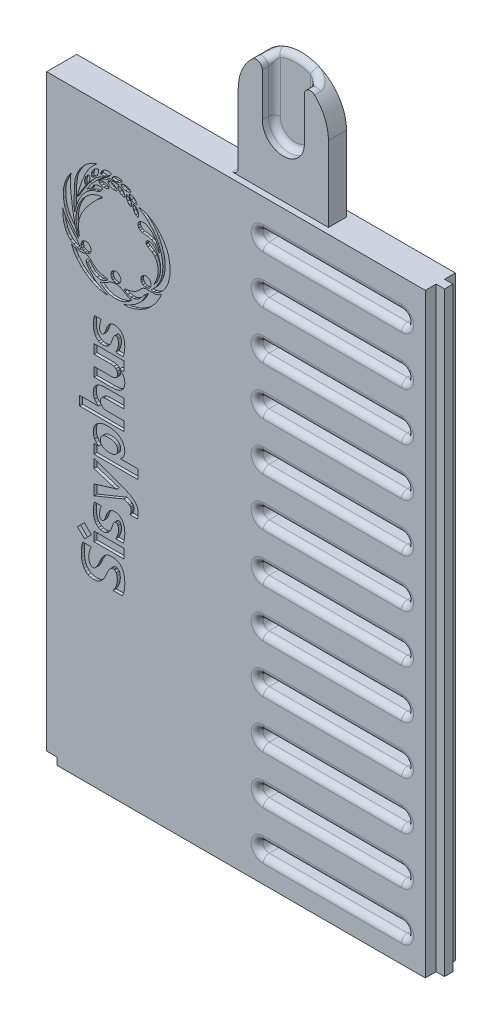
SolidWorks part; units mm, degrees
material "PVC Rigid"
ref_plane "Front Plane" through (0, 0, 0) normal (0, 0, 1) x (1, 0, 0)
ref_plane "Top Plane" through (0, 0, 0) normal (0, 1, 0) x (1, 0, 0)
ref_plane "Right Plane" through (0, 0, 0) normal (1, 0, 0) x (0, 0, -1)
sketch "Sketch1" plane through (0, 0, 0) normal (0, 1, 0) x (1, 0, 0)
  line L1 (-38.35, 2.5) -> (38.35, 2.5)
  line L2 (-38.35, 2.5) -> (-38.35, -2.5)
  line L3 (-38.35, -2.5) -> (38.35, -2.5)
  line L4 (38.35, 2.5) -> (38.35, -2.5)
  line L5 (-38.35, 2.5) -> (38.35, -2.5) construction
  line L6 (-38.35, -2.5) -> (38.35, 2.5) construction
  point P0 (0, 0)
  dimension "D1" = 5
  dimension "D2" = 76.7
extrude "Boss-Extrude1" add sketch "Sketch1" along normal blind 99
sketch "Sketch2" plane through (0, 99, 0) normal (0, 1, 0) x (1, 0, 0)
  line L0 (-7.5, -1.5) -> (-7.5, -0.5)
  line L1 (-6.5, 1.5) -> (7.5, 1.5)
  line L2 (-7.5, 0.5) -> (-7.5, -0.5)
  line L3 (-6.5, -1.5) -> (7.5, -1.5)
  line L5 (-7.5, 1.5) -> (7.5, -1.5) construction
  line L6 (-7.5, -1.5) -> (7.5, 1.5) construction
  line L7 (-7.5, 1.5) -> (-6.5, 1.5)
  line L8 (-7.5, -1.5) -> (-6.5, -1.5)
  line L9 (7.5, 1.5) -> (7.5, -1.5)
  line L12 (-7.5, 0.5) -> (-7.5, 1.5)
  point P0 (0, 0)
  dimension "D1" = 15
  dimension "D2" = 3
extrude "Boss-Extrude2" add sketch "Sketch2" along normal blind 20
sketch "Sketch3" plane through (0, 0, 1.5) normal (0, 0, 1) x (1, 0, 0)
  line L0 (-7.5, 119) -> (7.5, 119) construction
  line L1 (-3.5, 119) -> (3.5, 119)
  line L2 (-3.5, 119) -> (-3.5, 109)
  line L4 (3.5, 119) -> (3.5, 109)
  line L5 (-7.5, 119) -> (-7.5, 99) construction
  arc A0 (-3.5, 109) -> (3.5, 109) centre (0, 109) ccw
  dimension "D3" = 7.5
  dimension "D1" = 7
  dimension "D2" = 10
fillet "Fillet2" radius 1 1 edges at (-7.5, 99, 0)
sketch "Sketch4" plane through (0, 99, 0) normal (0, 1, 0) x (1, 0, 0)
  line L4 (-36.15, 0.5653) -> (-38.65, 0.5653)
  line L5 (-36.15, -1.4347) -> (-36.15, 0.5653)
  line L6 (-38.65, -1.4347) -> (-36.15, -1.4347)
  line L7 (-38.65, 0.5653) -> (-38.65, -1.4347)
  line L8 (-36.15, 0.5653) -> (-38.65, 0.5653)
  line L9 (-36.15, -1.4347) -> (-36.15, 0.5653)
  line L10 (-38.65, -1.4347) -> (-36.15, -1.4347)
  line L11 (-38.65, 0.5653) -> (-38.65, -1.4347)
  dimension "D1" = 0
sketch "Sketch5" plane through (0, 0, 0) normal (0, 0, 1) x (1, 0, 0)
  line L1 (24.6, -5) -> (60, -5)
  line L2 (24.6, -5) -> (24.6, 130)
  line L3 (24.6, 130) -> (60, 130)
  line L4 (60, -5) -> (60, 130)
extrude "Trim_door_beside_fixed_buttons" cut sketch "Sketch5" along normal blind 20 from offset 10 offset against normal yes
sketch "Sketch6" plane through (0, 0, 0) normal (0, 0, 1) x (1, 0, 0)
  line L0 (-39, -1) -> (-36.6, -1)
  line L1 (-36.6, -1) -> (-36.6, 1.2)
  line L2 (-36.6, 1.2) -> (-39, 1.2)
  line L3 (-39, 1.2) -> (-39, -1)
extrude "Clear_original_end_corner" cut sketch "Sketch6" along normal blind 10 from offset 5 offset against normal yes
sketch "Sketch8" plane through (0, 0, 0) normal (0, 0, 1) x (1, 0, 0)
  line L0 (24, 0) -> (26, 0)
  line L1 (26, 0) -> (26, 99)
  line L2 (26, 99) -> (24, 99)
  line L3 (24, 99) -> (24, 0)
extrude "Dust_overlap_tongue" add sketch "Sketch8" along normal blind 1.4 from offset 0.7 offset against normal yes
sketch "Sketch13" plane through (0, 0, 0) normal (0, 0, 1) x (1, 0, 0)
  line L0 (-25.7438, 29.8438) -> (-27.3063, 29.8438)
  line L1 (-27.3063, 29.8438) -> (-26.9938, 30.2875)
  line L2 (-26.9938, 30.2875) -> (-26.7688, 30.7688)
  line L3 (-26.7688, 30.7688) -> (-26.6375, 31.2688)
  line L4 (-26.6375, 31.2688) -> (-26.5938, 31.775)
  line L5 (-26.5938, 31.775) -> (-26.6438, 32.2938)
  line L6 (-26.6438, 32.2938) -> (-26.7063, 32.5)
  line L7 (-26.7063, 32.5) -> (-26.7938, 32.6625)
  line L8 (-26.7938, 32.6625) -> (-27.0188, 32.8875)
  line L9 (-27.0188, 32.8875) -> (-27.1563, 32.9438)
  line L10 (-27.1563, 32.9438) -> (-27.3, 32.9563)
  line L11 (-27.3, 32.9563) -> (-27.4938, 32.9313)
  line L12 (-27.4938, 32.9313) -> (-27.6688, 32.8438)
  line L13 (-27.6688, 32.8438) -> (-27.9625, 32.525)
  line L14 (-27.9625, 32.525) -> (-28.2313, 32.0438)
  line L15 (-28.2313, 32.0438) -> (-28.4875, 31.4375)
  line L16 (-28.4875, 31.4375) -> (-28.6688, 31.0563)
  line L17 (-28.6688, 31.0563) -> (-28.8687, 30.725)
  line L18 (-28.8687, 30.725) -> (-29.0875, 30.4438)
  line L19 (-29.0875, 30.4438) -> (-29.325, 30.2188)
  line L20 (-29.325, 30.2188) -> (-29.5813, 30.0438)
  line L21 (-29.5813, 30.0438) -> (-29.8687, 29.9125)
  line L22 (-29.8687, 29.9125) -> (-30.175, 29.8375)
  line L23 (-30.175, 29.8375) -> (-30.5125, 29.8125)
  line L24 (-30.5125, 29.8125) -> (-31.025, 29.8688)
  line L25 (-31.025, 29.8688) -> (-31.4563, 30.0313)
  line L26 (-31.4563, 30.0313) -> (-31.8125, 30.2938)
  line L27 (-31.8125, 30.2938) -> (-32.1, 30.6313)
  line L28 (-32.1, 30.6313) -> (-32.3188, 31.0438)
  line L29 (-32.3188, 31.0438) -> (-32.475, 31.5063)
  line L30 (-32.475, 31.5063) -> (-32.5625, 32.025)
  line L31 (-32.5625, 32.025) -> (-32.5938, 32.5625)
  line L32 (-32.5938, 32.5625) -> (-32.575, 33.0813)
  line L33 (-32.575, 33.0813) -> (-32.525, 33.5313)
  line L34 (-32.525, 33.5313) -> (-32.4438, 33.9375)
  line L35 (-32.4438, 33.9375) -> (-32.325, 34.3125)
  line L36 (-32.325, 34.3125) -> (-30.8625, 34.3125)
  line L37 (-30.8625, 34.3125) -> (-31.0813, 33.9313)
  line L38 (-31.0813, 33.9313) -> (-31.2313, 33.5)
  line L39 (-31.2313, 33.5) -> (-31.325, 33.0625)
  line L40 (-31.325, 33.0625) -> (-31.3563, 32.65)
  line L41 (-31.3563, 32.65) -> (-31.3, 32.1625)
  line L42 (-31.3, 32.1625) -> (-31.1563, 31.7938)
  line L43 (-31.1563, 31.7938) -> (-30.9375, 31.5563)
  line L44 (-30.9375, 31.5563) -> (-30.8, 31.4938)
  line L45 (-30.8, 31.4938) -> (-30.6438, 31.475)
  line L46 (-30.6438, 31.475) -> (-30.4813, 31.5)
  line L47 (-30.4813, 31.5) -> (-30.3313, 31.5688)
  line L48 (-30.3313, 31.5688) -> (-30.0688, 31.8313)
  line L49 (-30.0688, 31.8313) -> (-29.825, 32.2438)
  line L50 (-29.825, 32.2438) -> (-29.575, 32.8)
  line L51 (-29.575, 32.8) -> (-29.3938, 33.1938)
  line L52 (-29.3938, 33.1938) -> (-29.2, 33.55)
  line L53 (-29.2, 33.55) -> (-28.9937, 33.8625)
  line L54 (-28.9937, 33.8625) -> (-28.7563, 34.125)
  line L55 (-28.7563, 34.125) -> (-28.4875, 34.3375)
  line L56 (-28.4875, 34.3375) -> (-28.1875, 34.4938)
  line L57 (-28.1875, 34.4938) -> (-27.8438, 34.5875)
  line L58 (-27.8438, 34.5875) -> (-27.4438, 34.6188)
  line L59 (-27.4438, 34.6188) -> (-26.9, 34.5625)
  line L60 (-26.9, 34.5625) -> (-26.4563, 34.4)
  line L61 (-26.4563, 34.4) -> (-26.1, 34.1375)
  line L62 (-26.1, 34.1375) -> (-25.8125, 33.7938)
  line L63 (-25.8125, 33.7938) -> (-25.6, 33.3813)
  line L64 (-25.6, 33.3813) -> (-25.4625, 32.9063)
  line L65 (-25.4625, 32.9063) -> (-25.375, 32.3875)
  line L66 (-25.375, 32.3875) -> (-25.35, 31.8438)
  line L67 (-25.35, 31.8438) -> (-25.375, 31.2813)
  line L68 (-25.375, 31.2813) -> (-25.45, 30.7438)
  line L69 (-25.45, 30.7438) -> (-25.5688, 30.2625)
  line L70 (-25.5688, 30.2625) -> (-25.7438, 29.8438)
  line L71 (-32.0594, 34.9016) -> (-33.2172, 36.0594)
  line L72 (-33.2172, 36.0594) -> (-32.0594, 37.2172)
  line L73 (-32.0594, 37.2172) -> (-30.9016, 36.0594)
  line L74 (-30.9016, 36.0594) -> (-32.0594, 34.9016)
  line L75 (-25.475, 36.8188) -> (-25.475, 35.275)
  line L76 (-25.475, 35.275) -> (-30.475, 35.275)
  line L77 (-30.475, 35.275) -> (-30.475, 36.8188)
  line L78 (-30.475, 36.8188) -> (-25.475, 36.8188)
  line L79 (-25.6063, 37.5) -> (-26.8563, 37.5)
  line L80 (-26.8563, 37.5) -> (-26.6563, 37.8813)
  line L81 (-26.6563, 37.8813) -> (-26.5125, 38.2625)
  line L82 (-26.5125, 38.2625) -> (-26.425, 38.6313)
  line L83 (-26.425, 38.6313) -> (-26.4, 38.975)
  line L84 (-26.4, 38.975) -> (-26.425, 39.3438)
  line L85 (-26.425, 39.3438) -> (-26.5125, 39.6188)
  line L86 (-26.5125, 39.6188) -> (-26.6563, 39.8)
  line L87 (-26.6563, 39.8) -> (-26.8563, 39.8563)
  line L88 (-26.8563, 39.8563) -> (-26.9938, 39.8313)
  line L89 (-26.9938, 39.8313) -> (-27.1, 39.75)
  line L90 (-27.1, 39.75) -> (-27.2688, 39.475)
  line L91 (-27.2688, 39.475) -> (-27.4063, 39.1063)
  line L92 (-27.4063, 39.1063) -> (-27.5375, 38.7188)
  line L93 (-27.5375, 38.7188) -> (-27.775, 38.1938)
  line L94 (-27.775, 38.1938) -> (-28.075, 37.8125)
  line L95 (-28.075, 37.8125) -> (-28.475, 37.5813)
  line L96 (-28.475, 37.5813) -> (-28.7188, 37.5188)
  line L97 (-28.7188, 37.5188) -> (-29.0063, 37.5)
  line L98 (-29.0063, 37.5) -> (-29.3938, 37.5438)
  line L99 (-29.3938, 37.5438) -> (-29.725, 37.6813)
  line L100 (-29.725, 37.6813) -> (-30, 37.9)
  line L101 (-30, 37.9) -> (-30.225, 38.1688)
  line L102 (-30.225, 38.1688) -> (-30.3875, 38.5)
  line L103 (-30.3875, 38.5) -> (-30.5063, 38.8688)
  line L104 (-30.5063, 38.8688) -> (-30.575, 39.2688)
  line L105 (-30.575, 39.2688) -> (-30.6, 39.6875)
  line L106 (-30.6, 39.6875) -> (-30.5438, 40.3625)
  line L107 (-30.5438, 40.3625) -> (-30.3938, 41.0375)
  line L108 (-30.3938, 41.0375) -> (-29.2063, 41.0375)
  line L109 (-29.2063, 41.0375) -> (-29.3563, 40.7313)
  line L110 (-29.3563, 40.7313) -> (-29.4625, 40.4063)
  line L111 (-29.4625, 40.4063) -> (-29.525, 40.0813)
  line L112 (-29.525, 40.0813) -> (-29.55, 39.75)
  line L113 (-29.55, 39.75) -> (-29.5188, 39.4625)
  line L114 (-29.5188, 39.4625) -> (-29.4438, 39.2313)
  line L115 (-29.4438, 39.2313) -> (-29.3125, 39.0688)
  line L116 (-29.3125, 39.0688) -> (-29.125, 39.0063)
  line L117 (-29.125, 39.0063) -> (-29, 39.0313)
  line L118 (-29, 39.0313) -> (-28.8938, 39.0938)
  line L119 (-28.8938, 39.0938) -> (-28.725, 39.325)
  line L120 (-28.725, 39.325) -> (-28.6, 39.6438)
  line L121 (-28.6, 39.6438) -> (-28.4813, 39.9875)
  line L122 (-28.4813, 39.9875) -> (-28.25, 40.5438)
  line L123 (-28.25, 40.5438) -> (-27.95, 40.9688)
  line L124 (-27.95, 40.9688) -> (-27.7625, 41.125)
  line L125 (-27.7625, 41.125) -> (-27.55, 41.2438)
  line L126 (-27.55, 41.2438) -> (-27.3, 41.3125)
  line L127 (-27.3, 41.3125) -> (-27.0063, 41.3375)
  line L128 (-27.0063, 41.3375) -> (-26.5938, 41.2875)
  line L129 (-26.5938, 41.2875) -> (-26.2438, 41.1438)
  line L130 (-26.2438, 41.1438) -> (-25.9563, 40.9188)
  line L131 (-25.9563, 40.9188) -> (-25.7313, 40.6313)
  line L132 (-25.7313, 40.6313) -> (-25.5625, 40.2875)
  line L133 (-25.5625, 40.2875) -> (-25.4438, 39.8938)
  line L134 (-25.4438, 39.8938) -> (-25.375, 39.4688)
  line L135 (-25.375, 39.4688) -> (-25.35, 39.0313)
  line L136 (-25.35, 39.0313) -> (-25.4125, 38.2375)
  line L137 (-25.4125, 38.2375) -> (-25.6063, 37.5)
  line L138 (-30.475, 47.3188) -> (-25.075, 45.2875)
  line L139 (-25.075, 45.2875) -> (-24.6188, 45.0938)
  line L140 (-24.6188, 45.0938) -> (-24.2188, 44.875)
  line L141 (-24.2188, 44.875) -> (-23.8875, 44.6313)
  line L142 (-23.8875, 44.6313) -> (-23.6125, 44.3688)
  line L143 (-23.6125, 44.3688) -> (-23.4, 44.0813)
  line L144 (-23.4, 44.0813) -> (-23.2438, 43.7688)
  line L145 (-23.2438, 43.7688) -> (-23.1562, 43.4375)
  line L146 (-23.1562, 43.4375) -> (-23.125, 43.0813)
  line L147 (-23.125, 43.0813) -> (-23.1562, 42.5688)
  line L148 (-23.1562, 42.5688) -> (-23.2563, 42.1563)
  line L149 (-23.2563, 42.1563) -> (-24.4813, 42.1563)
  line L150 (-24.4813, 42.1563) -> (-24.3438, 42.4813)
  line L151 (-24.3438, 42.4813) -> (-24.3, 42.825)
  line L152 (-24.3, 42.825) -> (-24.3375, 43.1)
  line L153 (-24.3375, 43.1) -> (-24.4375, 43.3313)
  line L154 (-24.4375, 43.3313) -> (-24.6188, 43.5188)
  line L155 (-24.6188, 43.5188) -> (-24.8625, 43.6563)
  line L156 (-24.8625, 43.6563) -> (-25.4875, 43.9188)
  line L157 (-25.4875, 43.9188) -> (-30.475, 41.8875)
  line L158 (-30.475, 41.8875) -> (-30.475, 43.6)
  line L159 (-30.475, 43.6) -> (-27.4313, 44.5313)
  line L160 (-27.4313, 44.5313) -> (-27.125, 44.6125)
  line L161 (-27.125, 44.6125) -> (-26.7625, 44.6688)
  line L162 (-26.7625, 44.6688) -> (-26.7625, 44.6875)
  line L163 (-26.7625, 44.6875) -> (-27.0688, 44.75)
  line L164 (-27.0688, 44.75) -> (-27.425, 44.85)
  line L165 (-27.425, 44.85) -> (-30.475, 45.7938)
  line L166 (-30.475, 45.7938) -> (-30.475, 47.3188)
  line L167 (-26.0563, 49.4312) -> (-26.0563, 49.4125)
  line L168 (-26.0563, 49.4125) -> (-23.175, 49.4125)
  line L169 (-23.175, 49.4125) -> (-23.175, 47.8687)
  line L170 (-23.175, 47.8687) -> (-30.475, 47.8687)
  line L171 (-30.475, 47.8687) -> (-30.475, 49.4125)
  line L172 (-30.475, 49.4125) -> (-29.725, 49.4125)
  line L173 (-29.725, 49.4125) -> (-29.725, 49.4312)
  line L174 (-29.725, 49.4312) -> (-30.1063, 49.7437)
  line L175 (-30.1063, 49.7437) -> (-30.3813, 50.1187)
  line L176 (-30.3813, 50.1187) -> (-30.5438, 50.55)
  line L177 (-30.5438, 50.55) -> (-30.6, 51.0375)
  line L178 (-30.6, 51.0375) -> (-30.5563, 51.5)
  line L179 (-30.5563, 51.5) -> (-30.4313, 51.9)
  line L180 (-30.4313, 51.9) -> (-30.225, 52.25)
  line L181 (-30.225, 52.25) -> (-29.9313, 52.5437)
  line L182 (-29.9313, 52.5437) -> (-29.5688, 52.775)
  line L183 (-29.5688, 52.775) -> (-29.1438, 52.9375)
  line L184 (-29.1438, 52.9375) -> (-28.6625, 53.0375)
  line L185 (-28.6625, 53.0375) -> (-28.1188, 53.0687)
  line L186 (-28.1188, 53.0687) -> (-27.525, 53.0313)
  line L187 (-27.525, 53.0313) -> (-26.9875, 52.9125)
  line L188 (-26.9875, 52.9125) -> (-26.5188, 52.725)
  line L189 (-26.5188, 52.725) -> (-26.1125, 52.4562)
  line L190 (-26.1125, 52.4562) -> (-25.7813, 52.1187)
  line L191 (-25.7813, 52.1187) -> (-25.5438, 51.7375)
  line L192 (-25.5438, 51.7375) -> (-25.4, 51.3)
  line L193 (-25.4, 51.3) -> (-25.35, 50.8125)
  line L194 (-25.35, 50.8125) -> (-25.3938, 50.3875)
  line L195 (-25.3938, 50.3875) -> (-25.525, 50.0125)
  line L196 (-25.525, 50.0125) -> (-25.75, 49.6937)
  line L197 (-25.75, 49.6937) -> (-26.0563, 49.4312)
  line L198 (-28.1063, 49.3875) -> (-27.7063, 49.3875)
  line L199 (-27.7063, 49.3875) -> (-27.2375, 49.4562)
  line L200 (-27.2375, 49.4562) -> (-26.8625, 49.6625)
  line L201 (-26.8625, 49.6625) -> (-26.7188, 49.8125)
  line L202 (-26.7188, 49.8125) -> (-26.6188, 49.9812)
  line L203 (-26.6188, 49.9812) -> (-26.5563, 50.1687)
  line L204 (-26.5563, 50.1687) -> (-26.5375, 50.3812)
  line L205 (-26.5375, 50.3812) -> (-26.5625, 50.6312)
  line L206 (-26.5625, 50.6312) -> (-26.6375, 50.85)
  line L207 (-26.6375, 50.85) -> (-26.7625, 51.0375)
  line L208 (-26.7625, 51.0375) -> (-26.9438, 51.2)
  line L209 (-26.9438, 51.2) -> (-27.1688, 51.325)
  line L210 (-27.1688, 51.325) -> (-27.4375, 51.4187)
  line L211 (-27.4375, 51.4187) -> (-27.7438, 51.4688)
  line L212 (-27.7438, 51.4688) -> (-28.1, 51.4875)
  line L213 (-28.1, 51.4875) -> (-28.4063, 51.4688)
  line L214 (-28.4063, 51.4688) -> (-28.675, 51.425)
  line L215 (-28.675, 51.425) -> (-28.9, 51.3438)
  line L216 (-28.9, 51.3438) -> (-29.0813, 51.2312)
  line L217 (-29.0813, 51.2312) -> (-29.225, 51.0875)
  line L218 (-29.225, 51.0875) -> (-29.3313, 50.9125)
  line L219 (-29.3313, 50.9125) -> (-29.3938, 50.7062)
  line L220 (-29.3938, 50.7062) -> (-29.4125, 50.4625)
  line L221 (-29.4125, 50.4625) -> (-29.3875, 50.2375)
  line L222 (-29.3875, 50.2375) -> (-29.325, 50.0313)
  line L223 (-29.325, 50.0313) -> (-29.2125, 49.85)
  line L224 (-29.2125, 49.85) -> (-29.0562, 49.6875)
  line L225 (-29.0562, 49.6875) -> (-28.6375, 49.4625)
  line L226 (-28.6375, 49.4625) -> (-28.1063, 49.3875)
  line L227 (-25.475, 58.4187) -> (-25.475, 56.8812)
  line L228 (-25.475, 56.8812) -> (-28.3188, 56.8812)
  line L229 (-28.3188, 56.8812) -> (-28.8, 56.8312)
  line L230 (-28.8, 56.8312) -> (-29.1375, 56.6812)
  line L231 (-29.1375, 56.6812) -> (-29.3438, 56.4312)
  line L232 (-29.3438, 56.4312) -> (-29.4125, 56.0812)
  line L233 (-29.4125, 56.0812) -> (-29.3938, 55.8875)
  line L234 (-29.3938, 55.8875) -> (-29.3375, 55.7125)
  line L235 (-29.3375, 55.7125) -> (-29.2437, 55.5562)
  line L236 (-29.2437, 55.5562) -> (-29.1063, 55.4187)
  line L237 (-29.1063, 55.4187) -> (-28.7563, 55.225)
  line L238 (-28.7563, 55.225) -> (-28.325, 55.1625)
  line L239 (-28.325, 55.1625) -> (-25.475, 55.1625)
  line L240 (-25.475, 55.1625) -> (-25.475, 53.6187)
  line L241 (-25.475, 53.6187) -> (-32.875, 53.6187)
  line L242 (-32.875, 53.6187) -> (-32.875, 55.1625)
  line L243 (-32.875, 55.1625) -> (-29.7313, 55.1625)
  line L244 (-29.7313, 55.1625) -> (-29.7313, 55.1812)
  line L245 (-29.7313, 55.1812) -> (-30.1125, 55.4937)
  line L246 (-30.1125, 55.4937) -> (-30.3813, 55.85)
  line L247 (-30.3813, 55.85) -> (-30.5438, 56.2625)
  line L248 (-30.5438, 56.2625) -> (-30.6, 56.7187)
  line L249 (-30.6, 56.7187) -> (-30.5688, 57.1187)
  line L250 (-30.5688, 57.1187) -> (-30.4688, 57.4625)
  line L251 (-30.4688, 57.4625) -> (-30.3125, 57.7562)
  line L252 (-30.3125, 57.7562) -> (-30.0875, 57.9937)
  line L253 (-30.0875, 57.9937) -> (-29.7938, 58.1812)
  line L254 (-29.7938, 58.1812) -> (-29.4438, 58.3125)
  line L255 (-29.4438, 58.3125) -> (-29.025, 58.3937)
  line L256 (-29.025, 58.3937) -> (-28.5438, 58.4187)
  line L257 (-28.5438, 58.4187) -> (-25.475, 58.4187)
  line L258 (-25.475, 63.8) -> (-25.475, 62.2562)
  line L259 (-25.475, 62.2562) -> (-26.2375, 62.2562)
  line L260 (-26.2375, 62.2562) -> (-26.2375, 62.2375)
  line L261 (-26.2375, 62.2375) -> (-25.85, 61.925)
  line L262 (-25.85, 61.925) -> (-25.575, 61.5687)
  line L263 (-25.575, 61.5687) -> (-25.4063, 61.1625)
  line L264 (-25.4063, 61.1625) -> (-25.35, 60.7062)
  line L265 (-25.35, 60.7062) -> (-25.3813, 60.3)
  line L266 (-25.3813, 60.3) -> (-25.4813, 59.95)
  line L267 (-25.4813, 59.95) -> (-25.65, 59.65)
  line L268 (-25.65, 59.65) -> (-25.875, 59.4062)
  line L269 (-25.875, 59.4062) -> (-26.175, 59.2125)
  line L270 (-26.175, 59.2125) -> (-26.5375, 59.075)
  line L271 (-26.5375, 59.075) -> (-26.9625, 58.9937)
  line L272 (-26.9625, 58.9937) -> (-27.4563, 58.9687)
  line L273 (-27.4563, 58.9687) -> (-30.475, 58.9687)
  line L274 (-30.475, 58.9687) -> (-30.475, 60.5062)
  line L275 (-30.475, 60.5062) -> (-27.5938, 60.5062)
  line L276 (-27.5938, 60.5062) -> (-27.1313, 60.5562)
  line L277 (-27.1313, 60.5562) -> (-26.8, 60.7187)
  line L278 (-26.8, 60.7187) -> (-26.6063, 60.9812)
  line L279 (-26.6063, 60.9812) -> (-26.5375, 61.3437)
  line L280 (-26.5375, 61.3437) -> (-26.6063, 61.7187)
  line L281 (-26.6063, 61.7187) -> (-26.825, 62.0125)
  line L282 (-26.825, 62.0125) -> (-27.1688, 62.1937)
  line L283 (-27.1688, 62.1937) -> (-27.6125, 62.2562)
  line L284 (-27.6125, 62.2562) -> (-30.475, 62.2562)
  line L285 (-30.475, 62.2562) -> (-30.475, 63.8)
  line L286 (-30.475, 63.8) -> (-25.475, 63.8)
  line L287 (-25.6063, 64.35) -> (-26.8563, 64.35)
  line L288 (-26.8563, 64.35) -> (-26.6563, 64.7312)
  line L289 (-26.6563, 64.7312) -> (-26.5125, 65.1125)
  line L290 (-26.5125, 65.1125) -> (-26.425, 65.4812)
  line L291 (-26.425, 65.4812) -> (-26.4, 65.825)
  line L292 (-26.4, 65.825) -> (-26.425, 66.1937)
  line L293 (-26.425, 66.1937) -> (-26.5125, 66.4687)
  line L294 (-26.5125, 66.4687) -> (-26.6563, 66.65)
  line L295 (-26.6563, 66.65) -> (-26.8563, 66.7062)
  line L296 (-26.8563, 66.7062) -> (-26.9938, 66.6812)
  line L297 (-26.9938, 66.6812) -> (-27.1, 66.6)
  line L298 (-27.1, 66.6) -> (-27.2688, 66.325)
  line L299 (-27.2688, 66.325) -> (-27.4063, 65.9562)
  line L300 (-27.4063, 65.9562) -> (-27.5375, 65.5687)
  line L301 (-27.5375, 65.5687) -> (-27.775, 65.0437)
  line L302 (-27.775, 65.0437) -> (-28.075, 64.6625)
  line L303 (-28.075, 64.6625) -> (-28.475, 64.4312)
  line L304 (-28.475, 64.4312) -> (-28.7188, 64.3687)
  line L305 (-28.7188, 64.3687) -> (-29.0063, 64.35)
  line L306 (-29.0063, 64.35) -> (-29.3938, 64.3937)
  line L307 (-29.3938, 64.3937) -> (-29.725, 64.5312)
  line L308 (-29.725, 64.5312) -> (-30, 64.75)
  line L309 (-30, 64.75) -> (-30.225, 65.0187)
  line L310 (-30.225, 65.0187) -> (-30.3875, 65.35)
  line L311 (-30.3875, 65.35) -> (-30.5063, 65.7187)
  line L312 (-30.5063, 65.7187) -> (-30.575, 66.1187)
  line L313 (-30.575, 66.1187) -> (-30.6, 66.5375)
  line L314 (-30.6, 66.5375) -> (-30.5438, 67.2125)
  line L315 (-30.5438, 67.2125) -> (-30.3938, 67.8875)
  line L316 (-30.3938, 67.8875) -> (-29.2063, 67.8875)
  line L317 (-29.2063, 67.8875) -> (-29.3563, 67.5812)
  line L318 (-29.3563, 67.5812) -> (-29.4625, 67.2562)
  line L319 (-29.4625, 67.2562) -> (-29.525, 66.9312)
  line L320 (-29.525, 66.9312) -> (-29.55, 66.6)
  line L321 (-29.55, 66.6) -> (-29.5188, 66.3125)
  line L322 (-29.5188, 66.3125) -> (-29.4438, 66.0812)
  line L323 (-29.4438, 66.0812) -> (-29.3125, 65.9187)
  line L324 (-29.3125, 65.9187) -> (-29.125, 65.8562)
  line L325 (-29.125, 65.8562) -> (-29, 65.8812)
  line L326 (-29, 65.8812) -> (-28.8938, 65.9437)
  line L327 (-28.8938, 65.9437) -> (-28.725, 66.175)
  line L328 (-28.725, 66.175) -> (-28.6, 66.4937)
  line L329 (-28.6, 66.4937) -> (-28.4813, 66.8375)
  line L330 (-28.4813, 66.8375) -> (-28.25, 67.3937)
  line L331 (-28.25, 67.3937) -> (-27.95, 67.8187)
  line L332 (-27.95, 67.8187) -> (-27.7625, 67.975)
  line L333 (-27.7625, 67.975) -> (-27.55, 68.0937)
  line L334 (-27.55, 68.0937) -> (-27.3, 68.1625)
  line L335 (-27.3, 68.1625) -> (-27.0063, 68.1875)
  line L336 (-27.0063, 68.1875) -> (-26.5938, 68.1375)
  line L337 (-26.5938, 68.1375) -> (-26.2438, 67.9937)
  line L338 (-26.2438, 67.9937) -> (-25.9563, 67.7687)
  line L339 (-25.9563, 67.7687) -> (-25.7313, 67.4812)
  line L340 (-25.7313, 67.4812) -> (-25.5625, 67.1375)
  line L341 (-25.5625, 67.1375) -> (-25.4438, 66.7437)
  line L342 (-25.4438, 66.7437) -> (-25.375, 66.3187)
  line L343 (-25.375, 66.3187) -> (-25.35, 65.8812)
  line L344 (-25.35, 65.8812) -> (-25.4125, 65.0875)
  line L345 (-25.4125, 65.0875) -> (-25.6063, 64.35)
extrude "Sisyphus_side_wordmark_diamond_i_0p5mm" cut sketch "Sketch13" along normal blind 1 from offset 2
sketch "Sketch14" plane through (0, 0, 2.5) normal (0, 0, 1) x (1, 0, 0)
  line L1 (-3.35, 94) -> (21.65, 94)
  line L2 (-3.35, 94) -> (-3.35, 92)
  line L3 (-3.35, 92) -> (21.65, 92)
  line L4 (21.65, 94) -> (21.65, 92)
  line L5 (-38.35, 99) -> (-38.35, 1.2) construction
  line L6 (-38.35, 99) -> (24.6, 99) construction
  dimension "D1" = 25
  dimension "D2" = 2
  dimension "D3" = 35
  dimension "D4" = 5
extrude "Cut-Extrude2" cut sketch "Sketch14" against normal up to next
fillet "Fillet3" 2 edges at (-3.35, 92, 0) (-3.35, 94, 0) type full round first side face at (9.15, 92, 0) second side face at (9.15, 94, 0) middle face at (-3.35, 93, 0)
fillet "Fillet4" 2 edges at (21.65, 92, 0) (21.65, 94, 0) type full round first side face at (9.65, 92, 0) second side face at (9.65, 94, 0) middle face at (21.65, 93, 0)
fillet "Fillet5" radius 1 4 edges at (-3.35, 93, 2.5) (9.15, 94, 2.5) (21.65, 93, 2.5) (9.15, 92, 2.5)
fillet "Fillet6" radius 1 4 edges at (21.65, 93, -2.5) (9.15, 94, -2.5) (-3.35, 93, -2.5) (9.15, 92, -2.5)
pattern_linear "LPattern1" count 12 spacing 8 along (0, -1, 0) of "Fillet6", "Fillet5", "Fillet4", "Fillet3", "Cut-Extrude2"
fillet "Fillet7" 2 edges at (-7.5, 119, 0) (7.5, 119, 0) type full round first side face at (-7.5, 109.5, 0) second side face at (7.5, 109, 0) middle face at (0, 119, 0)
extrude "Cut-Extrude3" cut sketch "Sketch3" against normal blind 2
fillet "Fillet8" radius 1 6 edges at (-3.5, 118.1332, 0.5) (3.5, 118.1332, 0.5) (0, 119, -0.5) (3.5, 113.5666, -0.5) (0, 105.5, -0.5) (-3.5, 113.5666, -0.5)
sketch "Sketch15" plane through (0, 0, 0) normal (0, 0, 1) x (1, 0, 0)
  line L0 (-30.1147, 89.8918) -> (-30.014, 89.875)
  line L1 (-30.014, 89.875) -> (-30.3666, 89.5896)
  line L2 (-30.3666, 89.5896) -> (-31.0886, 88.8172)
  line L3 (-31.0886, 88.8172) -> (-31.4412, 88.3302)
  line L4 (-31.4412, 88.3302) -> (-31.8778, 87.5746)
  line L5 (-31.8778, 87.5746) -> (-32.4823, 86.181)
  line L6 (-32.4823, 86.181) -> (-32.9524, 84.7705)
  line L7 (-32.9524, 84.7705) -> (-33.2882, 83.5616)
  line L8 (-33.2882, 83.5616) -> (-32.5326, 84.8377)
  line L9 (-32.5326, 84.8377) -> (-31.7267, 86.0466)
  line L10 (-31.7267, 86.0466) -> (-31.8778, 85.9963)
  line L11 (-31.8778, 85.9963) -> (-31.9618, 86.0299)
  line L12 (-31.9618, 86.0299) -> (-32.0289, 86.2649)
  line L13 (-32.0289, 86.2649) -> (-32.0289, 86.6007)
  line L14 (-32.0289, 86.6007) -> (-31.8442, 87.1381)
  line L15 (-31.8442, 87.1381) -> (-31.4916, 87.541)
  line L16 (-31.4916, 87.541) -> (-31.2397, 87.6418)
  line L17 (-31.2397, 87.6418) -> (-31.1558, 87.306)
  line L18 (-31.1558, 87.306) -> (-31.2062, 86.8526)
  line L19 (-31.2062, 86.8526) -> (-31.3909, 86.416)
  line L20 (-31.3909, 86.416) -> (-31.0047, 86.9198)
  line L21 (-31.0047, 86.9198) -> (-30.3162, 87.6586)
  line L22 (-30.3162, 87.6586) -> (-29.8293, 88.0616)
  line L23 (-29.8293, 88.0616) -> (-29.0569, 88.5149)
  line L24 (-29.0569, 88.5149) -> (-28.5196, 88.7164)
  line L25 (-28.5196, 88.7164) -> (-27.7808, 88.8675)
  line L26 (-27.7808, 88.8675) -> (-27.0252, 88.8675)
  line L27 (-27.0252, 88.8675) -> (-26.236, 88.6996)
  line L28 (-26.236, 88.6996) -> (-27.2771, 88.7332)
  line L29 (-27.2771, 88.7332) -> (-28.2509, 88.5485)
  line L30 (-28.2509, 88.5485) -> (-29.0737, 88.1959)
  line L31 (-29.0737, 88.1959) -> (-30.0476, 87.4907)
  line L32 (-30.0476, 87.4907) -> (-30.9039, 86.5672)
  line L33 (-30.9039, 86.5672) -> (-31.7099, 85.4086)
  line L34 (-31.7099, 85.4086) -> (-31.1054, 85.8451)
  line L35 (-31.1054, 85.8451) -> (-30.8032, 85.9963)
  line L36 (-30.8032, 85.9963) -> (-30.7864, 86.1642)
  line L37 (-30.7864, 86.1642) -> (-30.6185, 86.4496)
  line L38 (-30.6185, 86.4496) -> (-30.3666, 86.6847)
  line L39 (-30.3666, 86.6847) -> (-30.0644, 86.8526)
  line L40 (-30.0644, 86.8526) -> (-29.6278, 86.9534)
  line L41 (-29.6278, 86.9534) -> (-29.2584, 86.9198)
  line L42 (-29.2584, 86.9198) -> (-29.0569, 86.8022)
  line L43 (-29.0569, 86.8022) -> (-29.1241, 86.6007)
  line L44 (-29.1241, 86.6007) -> (-29.4263, 86.2481)
  line L45 (-29.4263, 86.2481) -> (-29.6446, 86.097)
  line L46 (-29.6446, 86.097) -> (-29.9972, 85.9459)
  line L47 (-29.9972, 85.9459) -> (-30.4506, 85.8955)
  line L48 (-30.4506, 85.8955) -> (-31.1222, 85.5093)
  line L49 (-31.1222, 85.5093) -> (-31.7099, 85.0392)
  line L50 (-31.7099, 85.0392) -> (-32.1632, 84.569)
  line L51 (-32.1632, 84.569) -> (-32.7509, 83.7127)
  line L52 (-32.7509, 83.7127) -> (-33.1539, 82.8899)
  line L53 (-33.1539, 82.8899) -> (-33.5065, 81.8825)
  line L54 (-33.5065, 81.8825) -> (-33.6912, 81.0765)
  line L55 (-33.6912, 81.0765) -> (-33.7752, 81.8825)
  line L56 (-33.7752, 81.8825) -> (-33.7416, 84.9384)
  line L57 (-33.7416, 84.9384) -> (-33.5905, 86.0466)
  line L58 (-33.5905, 86.0466) -> (-33.3218, 86.8694)
  line L59 (-33.3218, 86.8694) -> (-32.7845, 87.8433)
  line L60 (-32.7845, 87.8433) -> (-31.9953, 88.75)
  line L61 (-31.9953, 88.75) -> (-31.5588, 89.1194)
  line L62 (-31.5588, 89.1194) -> (-30.9879, 89.5056)
  line L63 (-30.9879, 89.5056) -> (-30.1147, 89.8918)
  line L64 (-28.2677, 89.8078) -> (-27.764, 89.791)
  line L65 (-27.764, 89.791) -> (-27.6129, 89.7071)
  line L66 (-27.6129, 89.7071) -> (-27.6129, 89.6231)
  line L67 (-27.6129, 89.6231) -> (-27.764, 89.3377)
  line L68 (-27.764, 89.3377) -> (-28.0662, 89.0354)
  line L69 (-28.0662, 89.0354) -> (-28.3853, 88.8507)
  line L70 (-28.3853, 88.8507) -> (-28.7211, 88.75)
  line L71 (-28.7211, 88.75) -> (-29.3256, 88.7668)
  line L72 (-29.3256, 88.7668) -> (-29.3591, 88.8675)
  line L73 (-29.3591, 88.8675) -> (-29.3088, 89.0522)
  line L74 (-29.3088, 89.0522) -> (-29.1576, 89.3041)
  line L75 (-29.1576, 89.3041) -> (-28.9058, 89.5392)
  line L76 (-28.9058, 89.5392) -> (-28.57, 89.7239)
  line L77 (-28.57, 89.7239) -> (-28.2677, 89.8078)
  line L78 (-26.6054, 89.7239) -> (-26.0345, 89.6567)
  line L79 (-26.0345, 89.6567) -> (-25.8498, 89.5728)
  line L80 (-25.8498, 89.5728) -> (-25.7994, 89.4552)
  line L81 (-25.7994, 89.4552) -> (-26.1521, 89.1362)
  line L82 (-26.1521, 89.1362) -> (-26.6726, 88.9683)
  line L83 (-26.6726, 88.9683) -> (-27.0252, 88.9515)
  line L84 (-27.0252, 88.9515) -> (-27.2603, 89.0019)
  line L85 (-27.2603, 89.0019) -> (-27.4618, 89.1026)
  line L86 (-27.4618, 89.1026) -> (-27.4618, 89.2201)
  line L87 (-27.4618, 89.2201) -> (-27.1259, 89.556)
  line L88 (-27.1259, 89.556) -> (-26.6054, 89.7239)
  line L89 (-29.8629, 89.2705) -> (-29.7621, 89.2705)
  line L90 (-29.7621, 89.2705) -> (-29.7118, 89.2034)
  line L91 (-29.7118, 89.2034) -> (-29.7118, 88.9011)
  line L92 (-29.7118, 88.9011) -> (-29.93, 88.2799)
  line L93 (-29.93, 88.2799) -> (-30.2994, 87.8433)
  line L94 (-30.2994, 87.8433) -> (-30.7528, 87.625)
  line L95 (-30.7528, 87.625) -> (-30.8871, 87.6586)
  line L96 (-30.8871, 87.6586) -> (-30.9039, 88.0784)
  line L97 (-30.9039, 88.0784) -> (-30.7192, 88.5989)
  line L98 (-30.7192, 88.5989) -> (-30.3498, 89.0187)
  line L99 (-30.3498, 89.0187) -> (-29.8629, 89.2705)
  line L100 (-25.514, 89.1866) -> (-25.1278, 89.1866)
  line L101 (-25.1278, 89.1866) -> (-24.8759, 89.1194)
  line L102 (-24.8759, 89.1194) -> (-24.5401, 88.9347)
  line L103 (-24.5401, 88.9347) -> (-24.3554, 88.7332)
  line L104 (-24.3554, 88.7332) -> (-24.3554, 88.666)
  line L105 (-24.3554, 88.666) -> (-24.4562, 88.5821)
  line L106 (-24.4562, 88.5821) -> (-24.8591, 88.4646)
  line L107 (-24.8591, 88.4646) -> (-25.2453, 88.4478)
  line L108 (-25.2453, 88.4478) -> (-25.4636, 88.4981)
  line L109 (-25.4636, 88.4981) -> (-25.7491, 88.6325)
  line L110 (-25.7491, 88.6325) -> (-25.9674, 88.8172)
  line L111 (-25.9674, 88.8172) -> (-25.9674, 88.9851)
  line L112 (-25.9674, 88.9851) -> (-25.7155, 89.1362)
  line L113 (-25.7155, 89.1362) -> (-25.514, 89.1866)
  line L114 (-26.4879, 88.5317) -> (-26.0513, 88.4813)
  line L115 (-26.0513, 88.4813) -> (-25.7994, 88.347)
  line L116 (-25.7994, 88.347) -> (-25.5812, 88.1455)
  line L117 (-25.5812, 88.1455) -> (-25.3629, 87.7593)
  line L118 (-25.3629, 87.7593) -> (-25.3293, 87.4067)
  line L119 (-25.3293, 87.4067) -> (-25.3797, 87.3899)
  line L120 (-25.3797, 87.3899) -> (-25.5979, 87.3899)
  line L121 (-25.5979, 87.3899) -> (-25.8498, 87.4739)
  line L122 (-25.8498, 87.4739) -> (-26.236, 87.7593)
  line L123 (-26.236, 87.7593) -> (-26.5047, 88.2631)
  line L124 (-26.5047, 88.2631) -> (-26.4879, 88.5317)
  line L125 (-27.7472, 88.4646) -> (-27.3946, 88.431)
  line L126 (-27.3946, 88.431) -> (-27.1595, 88.347)
  line L127 (-27.1595, 88.347) -> (-26.7565, 88.028)
  line L128 (-26.7565, 88.028) -> (-26.6222, 87.709)
  line L129 (-26.6222, 87.709) -> (-26.7565, 87.625)
  line L130 (-26.7565, 87.625) -> (-27.042, 87.5914)
  line L131 (-27.042, 87.5914) -> (-27.2771, 87.5914)
  line L132 (-27.2771, 87.5914) -> (-27.5793, 87.6754)
  line L133 (-27.5793, 87.6754) -> (-27.7976, 87.7929)
  line L134 (-27.7976, 87.7929) -> (-28.0494, 88.028)
  line L135 (-28.0494, 88.028) -> (-28.1502, 88.1791)
  line L136 (-28.1502, 88.1791) -> (-28.167, 88.3134)
  line L137 (-28.167, 88.3134) -> (-28.0494, 88.3974)
  line L138 (-28.0494, 88.3974) -> (-27.7472, 88.4646)
  line L139 (-24.5569, 88.2966) -> (-24.1371, 88.2631)
  line L140 (-24.1371, 88.2631) -> (-23.667, 87.9944)
  line L141 (-23.667, 87.9944) -> (-23.3647, 87.5578)
  line L142 (-23.3647, 87.5578) -> (-23.3312, 87.3731)
  line L143 (-23.3312, 87.3731) -> (-23.4151, 87.3228)
  line L144 (-23.4151, 87.3228) -> (-23.7845, 87.3396)
  line L145 (-23.7845, 87.3396) -> (-24.0532, 87.4403)
  line L146 (-24.0532, 87.4403) -> (-24.2715, 87.5914)
  line L147 (-24.2715, 87.5914) -> (-24.5905, 88.028)
  line L148 (-24.5905, 88.028) -> (-24.6241, 88.2631)
  line L149 (-24.6241, 88.2631) -> (-24.5569, 88.2966)
  line L150 (-25.0606, 88.028) -> (-24.7416, 87.9104)
  line L151 (-24.7416, 87.9104) -> (-24.4058, 87.541)
  line L152 (-24.4058, 87.541) -> (-24.2379, 87.0373)
  line L153 (-24.2379, 87.0373) -> (-24.2379, 86.7519)
  line L154 (-24.2379, 86.7519) -> (-24.305, 86.584)
  line L155 (-24.305, 86.584) -> (-24.4058, 86.584)
  line L156 (-24.4058, 86.584) -> (-24.6241, 86.7183)
  line L157 (-24.6241, 86.7183) -> (-24.9263, 87.0709)
  line L158 (-24.9263, 87.0709) -> (-25.111, 87.5914)
  line L159 (-25.111, 87.5914) -> (-25.111, 87.9104)
  line L160 (-25.111, 87.9104) -> (-25.0606, 88.028)
  line L161 (-29.0065, 87.9272) -> (-28.6371, 87.9104)
  line L162 (-28.6371, 87.9104) -> (-28.3685, 87.8265)
  line L163 (-28.3685, 87.8265) -> (-28.1166, 87.6754)
  line L164 (-28.1166, 87.6754) -> (-27.9487, 87.4907)
  line L165 (-27.9487, 87.4907) -> (-27.9487, 87.4067)
  line L166 (-27.9487, 87.4067) -> (-28.0494, 87.306)
  line L167 (-28.0494, 87.306) -> (-28.3517, 87.1716)
  line L168 (-28.3517, 87.1716) -> (-28.6203, 87.1381)
  line L169 (-28.6203, 87.1381) -> (-28.8386, 87.1213)
  line L170 (-28.8386, 87.1213) -> (-29.2248, 87.2052)
  line L171 (-29.2248, 87.2052) -> (-29.4935, 87.3563)
  line L172 (-29.4935, 87.3563) -> (-29.6446, 87.5243)
  line L173 (-29.6446, 87.5243) -> (-29.6446, 87.6418)
  line L174 (-29.6446, 87.6418) -> (-29.4599, 87.7929)
  line L175 (-29.4599, 87.7929) -> (-29.0065, 87.9272)
  line L176 (-23.9021, 87.1549) -> (-23.5326, 86.9869)
  line L177 (-23.5326, 86.9869) -> (-23.2808, 86.7183)
  line L178 (-23.2808, 86.7183) -> (-23.1465, 86.4664)
  line L179 (-23.1465, 86.4664) -> (-23.0625, 86.1138)
  line L180 (-23.0625, 86.1138) -> (-23.0625, 85.8451)
  line L181 (-23.0625, 85.8451) -> (-23.1632, 85.5933)
  line L182 (-23.1632, 85.5933) -> (-23.5326, 85.778)
  line L183 (-23.5326, 85.778) -> (-23.8853, 86.2649)
  line L184 (-23.8853, 86.2649) -> (-24.0028, 86.7687)
  line L185 (-24.0028, 86.7687) -> (-23.9692, 87.0709)
  line L186 (-23.9692, 87.0709) -> (-23.9021, 87.1549)
  line L187 (-22.9618, 87.1381) -> (-22.2397, 87.0205)
  line L188 (-22.2397, 87.0205) -> (-21.6017, 86.7854)
  line L189 (-21.6017, 86.7854) -> (-20.7453, 86.2985)
  line L190 (-20.7453, 86.2985) -> (-20.0569, 85.7444)
  line L191 (-20.0569, 85.7444) -> (-19.4692, 85.1399)
  line L192 (-19.4692, 85.1399) -> (-18.8479, 84.3004)
  line L193 (-18.8479, 84.3004) -> (-18.3442, 83.3601)
  line L194 (-18.3442, 83.3601) -> (-18.0588, 82.5541)
  line L195 (-18.0588, 82.5541) -> (-17.8573, 81.4459)
  line L196 (-17.8573, 81.4459) -> (-17.8237, 80.4552)
  line L197 (-17.8237, 80.4552) -> (-17.8909, 79.7164)
  line L198 (-17.8909, 79.7164) -> (-18.0924, 78.8097)
  line L199 (-18.0924, 78.8097) -> (-18.445, 77.9534)
  line L200 (-18.445, 77.9534) -> (-18.8479, 77.3321)
  line L201 (-18.8479, 77.3321) -> (-19.4021, 76.7444)
  line L202 (-19.4021, 76.7444) -> (-19.7379, 76.5093)
  line L203 (-19.7379, 76.5093) -> (-20.0065, 76.3918)
  line L204 (-20.0065, 76.3918) -> (-20.4767, 76.2407)
  line L205 (-20.4767, 76.2407) -> (-20.9972, 76.2407)
  line L206 (-20.9972, 76.2407) -> (-20.3927, 76.8619)
  line L207 (-20.3927, 76.8619) -> (-19.9394, 77.4664)
  line L208 (-19.9394, 77.4664) -> (-19.486, 78.2892)
  line L209 (-19.486, 78.2892) -> (-19.2174, 79.0448)
  line L210 (-19.2174, 79.0448) -> (-19.0662, 79.8172)
  line L211 (-19.0662, 79.8172) -> (-19.0326, 80.6735)
  line L212 (-19.0326, 80.6735) -> (-19.1166, 81.5299)
  line L213 (-19.1166, 81.5299) -> (-19.2845, 82.3022)
  line L214 (-19.2845, 82.3022) -> (-19.7379, 83.5448)
  line L215 (-19.7379, 83.5448) -> (-20.1912, 84.3843)
  line L216 (-20.1912, 84.3843) -> (-20.6614, 85.056)
  line L217 (-20.6614, 85.056) -> (-21.5849, 86.0466)
  line L218 (-21.5849, 86.0466) -> (-22.2565, 86.584)
  line L219 (-22.2565, 86.584) -> (-22.9618, 87.0205)
  line L220 (-22.9618, 87.0205) -> (-23.0121, 87.0709)
  line L221 (-23.0121, 87.0709) -> (-22.9618, 87.1381)
  line L222 (-34.3125, 86.4328) -> (-34.3965, 85.4925)
  line L223 (-34.3965, 85.4925) -> (-34.3965, 84.4347)
  line L224 (-34.3965, 84.4347) -> (-34.0271, 81.3787)
  line L225 (-34.0271, 81.3787) -> (-33.6241, 79.2966)
  line L226 (-33.6241, 79.2966) -> (-33.3554, 78.4403)
  line L227 (-33.3554, 78.4403) -> (-32.986, 77.5504)
  line L228 (-32.986, 77.5504) -> (-33.5233, 78.1716)
  line L229 (-33.5233, 78.1716) -> (-34.3965, 79.2799)
  line L230 (-34.3965, 79.2799) -> (-34.9002, 80.069)
  line L231 (-34.9002, 80.069) -> (-35.3535, 81.1604)
  line L232 (-35.3535, 81.1604) -> (-35.555, 82.2183)
  line L233 (-35.555, 82.2183) -> (-35.5718, 83.2425)
  line L234 (-35.5718, 83.2425) -> (-35.4879, 83.8974)
  line L235 (-35.4879, 83.8974) -> (-35.3368, 84.5187)
  line L236 (-35.3368, 84.5187) -> (-34.917, 85.5261)
  line L237 (-34.917, 85.5261) -> (-34.3125, 86.4328)
  line L238 (-29.4095, 85.5429) -> (-29.0401, 85.5429)
  line L239 (-29.0401, 85.5429) -> (-29.0233, 85.4925)
  line L240 (-29.0233, 85.4925) -> (-29.9132, 84.8209)
  line L241 (-29.9132, 84.8209) -> (-30.82, 83.8974)
  line L242 (-30.82, 83.8974) -> (-31.8946, 82.5709)
  line L243 (-31.8946, 82.5709) -> (-32.583, 81.4459)
  line L244 (-32.583, 81.4459) -> (-32.9356, 80.472)
  line L245 (-32.9356, 80.472) -> (-33.0532, 79.6828)
  line L246 (-33.0532, 79.6828) -> (-33.0364, 78.9608)
  line L247 (-33.0364, 78.9608) -> (-32.8853, 77.9534)
  line L248 (-32.8853, 77.9534) -> (-33.2715, 78.9272)
  line L249 (-33.2715, 78.9272) -> (-33.4562, 80.0187)
  line L250 (-33.4562, 80.0187) -> (-33.4394, 80.8246)
  line L251 (-33.4394, 80.8246) -> (-33.3386, 81.4795)
  line L252 (-33.3386, 81.4795) -> (-33.1707, 82.1175)
  line L253 (-33.1707, 82.1175) -> (-32.9524, 82.6884)
  line L254 (-32.9524, 82.6884) -> (-32.3647, 83.7127)
  line L255 (-32.3647, 83.7127) -> (-31.5756, 84.5522)
  line L256 (-31.5756, 84.5522) -> (-31.0718, 84.9216)
  line L257 (-31.0718, 84.9216) -> (-30.5513, 85.2071)
  line L258 (-30.5513, 85.2071) -> (-29.9804, 85.4254)
  line L259 (-29.9804, 85.4254) -> (-29.4095, 85.5429)
  line L260 (-22.4076, 85.3582) -> (-22.055, 85.3414)
  line L261 (-22.055, 85.3414) -> (-21.6688, 85.2239)
  line L262 (-21.6688, 85.2239) -> (-21.1315, 84.9049)
  line L263 (-21.1315, 84.9049) -> (-20.7621, 84.569)
  line L264 (-20.7621, 84.569) -> (-20.0905, 83.6287)
  line L265 (-20.0905, 83.6287) -> (-19.7211, 82.8228)
  line L266 (-19.7211, 82.8228) -> (-19.5364, 82.1511)
  line L267 (-19.5364, 82.1511) -> (-19.8554, 82.6045)
  line L268 (-19.8554, 82.6045) -> (-20.3256, 83.1586)
  line L269 (-20.3256, 83.1586) -> (-20.93, 83.5448)
  line L270 (-20.93, 83.5448) -> (-21.5009, 83.7127)
  line L271 (-21.5009, 83.7127) -> (-22.4748, 83.8134)
  line L272 (-22.4748, 83.8134) -> (-22.7938, 83.9478)
  line L273 (-22.7938, 83.9478) -> (-23.0121, 84.1325)
  line L274 (-23.0121, 84.1325) -> (-23.18, 84.4851)
  line L275 (-23.18, 84.4851) -> (-23.1297, 84.9049)
  line L276 (-23.1297, 84.9049) -> (-22.861, 85.2071)
  line L277 (-22.861, 85.2071) -> (-22.4076, 85.3582)
  line L278 (-21.4674, 83.1082) -> (-21.1483, 83.1082)
  line L279 (-21.1483, 83.1082) -> (-20.93, 83.041)
  line L280 (-20.93, 83.041) -> (-20.5606, 82.8228)
  line L281 (-20.5606, 82.8228) -> (-20.1912, 82.4701)
  line L282 (-20.1912, 82.4701) -> (-19.7379, 81.7481)
  line L283 (-19.7379, 81.7481) -> (-19.4524, 80.8078)
  line L284 (-19.4524, 80.8078) -> (-19.4021, 79.8004)
  line L285 (-19.4021, 79.8004) -> (-19.57, 78.8601)
  line L286 (-19.57, 78.8601) -> (-19.9897, 77.903)
  line L287 (-19.9897, 77.903) -> (-20.4767, 77.2985)
  line L288 (-20.4767, 77.2985) -> (-20.5103, 77.2649)
  line L289 (-20.5103, 77.2649) -> (-20.1073, 78.1213)
  line L290 (-20.1073, 78.1213) -> (-19.889, 78.8601)
  line L291 (-19.889, 78.8601) -> (-19.8218, 79.3302)
  line L292 (-19.8218, 79.3302) -> (-19.8554, 80.2034)
  line L293 (-19.8554, 80.2034) -> (-20.0401, 80.8414)
  line L294 (-20.0401, 80.8414) -> (-20.3927, 81.4291)
  line L295 (-20.3927, 81.4291) -> (-20.8293, 81.8321)
  line L296 (-20.8293, 81.8321) -> (-21.5177, 82.1847)
  line L297 (-21.5177, 82.1847) -> (-21.7696, 82.4366)
  line L298 (-21.7696, 82.4366) -> (-21.82, 82.5541)
  line L299 (-21.82, 82.5541) -> (-21.8032, 82.8396)
  line L300 (-21.8032, 82.8396) -> (-21.6353, 83.041)
  line L301 (-21.6353, 83.041) -> (-21.4674, 83.1082)
  line L302 (-35.6726, 80.6903) -> (-35.2864, 79.9347)
  line L303 (-35.2864, 79.9347) -> (-34.8498, 79.2463)
  line L304 (-34.8498, 79.2463) -> (-33.2882, 77.3993)
  line L305 (-33.2882, 77.3993) -> (-32.667, 76.291)
  line L306 (-32.667, 76.291) -> (-32.6838, 76.2407)
  line L307 (-32.6838, 76.2407) -> (-33.2547, 76.2407)
  line L308 (-33.2547, 76.2407) -> (-33.8759, 76.4254)
  line L309 (-33.8759, 76.4254) -> (-34.3965, 76.7612)
  line L310 (-34.3965, 76.7612) -> (-34.8498, 77.2817)
  line L311 (-34.8498, 77.2817) -> (-35.2528, 78.0373)
  line L312 (-35.2528, 78.0373) -> (-35.5047, 78.8265)
  line L313 (-35.5047, 78.8265) -> (-35.639, 79.6325)
  line L314 (-35.639, 79.6325) -> (-35.6726, 80.6903)
  line L315 (-31.9114, 77.8526) -> (-31.5924, 77.8358)
  line L316 (-31.5924, 77.8358) -> (-31.2565, 77.6679)
  line L317 (-31.2565, 77.6679) -> (-31.0718, 77.4496)
  line L318 (-31.0718, 77.4496) -> (-30.9543, 77.1138)
  line L319 (-30.9543, 77.1138) -> (-30.9711, 76.8116)
  line L320 (-30.9711, 76.8116) -> (-31.1558, 76.459)
  line L321 (-31.1558, 76.459) -> (-31.3573, 76.291)
  line L322 (-31.3573, 76.291) -> (-31.6763, 76.1903)
  line L323 (-31.6763, 76.1903) -> (-31.9618, 76.1903)
  line L324 (-31.9618, 76.1903) -> (-32.264, 76.3246)
  line L325 (-32.264, 76.3246) -> (-32.4823, 76.5429)
  line L326 (-32.4823, 76.5429) -> (-32.6166, 76.8787)
  line L327 (-32.6166, 76.8787) -> (-32.6166, 77.1642)
  line L328 (-32.6166, 77.1642) -> (-32.4823, 77.5)
  line L329 (-32.4823, 77.5) -> (-32.264, 77.7183)
  line L330 (-32.264, 77.7183) -> (-31.9114, 77.8526)
  line L331 (-21.9879, 77.8526) -> (-21.6688, 77.8526)
  line L332 (-21.6688, 77.8526) -> (-21.3498, 77.7183)
  line L333 (-21.3498, 77.7183) -> (-21.0979, 77.4496)
  line L334 (-21.0979, 77.4496) -> (-20.9972, 77.181)
  line L335 (-20.9972, 77.181) -> (-20.9972, 76.8451)
  line L336 (-20.9972, 76.8451) -> (-21.1651, 76.4925)
  line L337 (-21.1651, 76.4925) -> (-21.3666, 76.3078)
  line L338 (-21.3666, 76.3078) -> (-21.6856, 76.1903)
  line L339 (-21.6856, 76.1903) -> (-22.0215, 76.1903)
  line L340 (-22.0215, 76.1903) -> (-22.3237, 76.3246)
  line L341 (-22.3237, 76.3246) -> (-22.5756, 76.6101)
  line L342 (-22.5756, 76.6101) -> (-22.6595, 76.8451)
  line L343 (-22.6595, 76.8451) -> (-22.6595, 77.181)
  line L344 (-22.6595, 77.181) -> (-22.5588, 77.4496)
  line L345 (-22.5588, 77.4496) -> (-22.3069, 77.7183)
  line L346 (-22.3069, 77.7183) -> (-21.9879, 77.8526)
  line L347 (-19.3013, 76.459) -> (-19.2845, 76.3918)
  line L348 (-19.2845, 76.3918) -> (-19.6707, 75.5858)
  line L349 (-19.6707, 75.5858) -> (-20.2752, 74.6623)
  line L350 (-20.2752, 74.6623) -> (-21.2155, 73.6381)
  line L351 (-21.2155, 73.6381) -> (-21.8368, 73.1343)
  line L352 (-21.8368, 73.1343) -> (-22.6427, 72.6306)
  line L353 (-22.6427, 72.6306) -> (-23.583, 72.2108)
  line L354 (-23.583, 72.2108) -> (-24.5401, 71.959)
  line L355 (-24.5401, 71.959) -> (-25.4972, 71.8918)
  line L356 (-25.4972, 71.8918) -> (-24.3554, 72.4291)
  line L357 (-24.3554, 72.4291) -> (-23.6166, 72.8825)
  line L358 (-23.6166, 72.8825) -> (-22.8274, 73.5541)
  line L359 (-22.8274, 73.5541) -> (-22.4244, 74.041)
  line L360 (-22.4244, 74.041) -> (-22.0382, 74.6287)
  line L361 (-22.0382, 74.6287) -> (-21.8032, 75.1325)
  line L362 (-21.8032, 75.1325) -> (-22.139, 74.9142)
  line L363 (-22.139, 74.9142) -> (-22.5588, 74.3937)
  line L364 (-22.5588, 74.3937) -> (-22.9282, 74.041)
  line L365 (-22.9282, 74.041) -> (-23.2472, 73.8228)
  line L366 (-23.2472, 73.8228) -> (-23.7509, 73.6213)
  line L367 (-23.7509, 73.6213) -> (-24.3218, 73.5709)
  line L368 (-24.3218, 73.5709) -> (-24.8424, 73.6884)
  line L369 (-24.8424, 73.6884) -> (-25.2789, 73.9235)
  line L370 (-25.2789, 73.9235) -> (-25.43, 74.0746)
  line L371 (-25.43, 74.0746) -> (-25.43, 74.1922)
  line L372 (-25.43, 74.1922) -> (-25.2621, 74.2761)
  line L373 (-25.2621, 74.2761) -> (-24.3722, 74.4104)
  line L374 (-24.3722, 74.4104) -> (-23.7006, 74.6791)
  line L375 (-23.7006, 74.6791) -> (-23.0961, 75.1157)
  line L376 (-23.0961, 75.1157) -> (-22.5252, 75.7201)
  line L377 (-22.5252, 75.7201) -> (-22.1894, 75.9216)
  line L378 (-22.1894, 75.9216) -> (-21.8535, 76.0056)
  line L379 (-21.8535, 76.0056) -> (-20.93, 75.9552)
  line L380 (-20.93, 75.9552) -> (-20.3424, 75.9888)
  line L381 (-20.3424, 75.9888) -> (-19.7882, 76.1567)
  line L382 (-19.7882, 76.1567) -> (-19.3013, 76.459)
  line L383 (-34.2453, 76.291) -> (-33.8088, 76.0896)
  line L384 (-33.8088, 76.0896) -> (-33.2379, 75.9552)
  line L385 (-33.2379, 75.9552) -> (-32.7174, 75.9384)
  line L386 (-32.7174, 75.9384) -> (-31.945, 76.0056)
  line L387 (-31.945, 76.0056) -> (-31.5084, 75.9384)
  line L388 (-31.5084, 75.9384) -> (-31.0886, 75.7034)
  line L389 (-31.0886, 75.7034) -> (-30.5513, 75.1157)
  line L390 (-30.5513, 75.1157) -> (-29.9636, 74.6791)
  line L391 (-29.9636, 74.6791) -> (-29.3256, 74.4104)
  line L392 (-29.3256, 74.4104) -> (-28.3517, 74.2593)
  line L393 (-28.3517, 74.2593) -> (-28.2509, 74.1922)
  line L394 (-28.2509, 74.1922) -> (-28.2677, 74.041)
  line L395 (-28.2677, 74.041) -> (-28.4524, 73.8899)
  line L396 (-28.4524, 73.8899) -> (-29.0065, 73.6381)
  line L397 (-29.0065, 73.6381) -> (-29.2584, 73.5877)
  line L398 (-29.2584, 73.5877) -> (-29.9468, 73.6381)
  line L399 (-29.9468, 73.6381) -> (-30.417, 73.8396)
  line L400 (-30.417, 73.8396) -> (-30.6688, 74.0075)
  line L401 (-30.6688, 74.0075) -> (-31.0886, 74.4104)
  line L402 (-31.0886, 74.4104) -> (-31.5588, 74.9813)
  line L403 (-31.5588, 74.9813) -> (-31.8442, 75.1325)
  line L404 (-31.8442, 75.1325) -> (-31.6595, 74.7127)
  line L405 (-31.6595, 74.7127) -> (-31.2565, 74.0746)
  line L406 (-31.2565, 74.0746) -> (-30.4841, 73.2183)
  line L407 (-30.4841, 73.2183) -> (-30.014, 72.8489)
  line L408 (-30.014, 72.8489) -> (-29.1241, 72.3116)
  line L409 (-29.1241, 72.3116) -> (-28.2174, 71.9086)
  line L410 (-28.2174, 71.9086) -> (-28.805, 71.9254)
  line L411 (-28.805, 71.9254) -> (-29.93, 72.194)
  line L412 (-29.93, 72.194) -> (-30.8032, 72.5634)
  line L413 (-30.8032, 72.5634) -> (-31.8778, 73.2351)
  line L414 (-31.8778, 73.2351) -> (-32.5494, 73.806)
  line L415 (-32.5494, 73.806) -> (-33.3386, 74.6791)
  line L416 (-33.3386, 74.6791) -> (-33.8591, 75.4515)
  line L417 (-33.8591, 75.4515) -> (-34.2453, 76.291)
  line L418 (-26.8741, 76.0056) -> (-26.6054, 75.9888)
  line L419 (-26.6054, 75.9888) -> (-26.3368, 75.8545)
  line L420 (-26.3368, 75.8545) -> (-26.1185, 75.6194)
  line L421 (-26.1185, 75.6194) -> (-26.0009, 75.3172)
  line L422 (-26.0009, 75.3172) -> (-26.0009, 75.0149)
  line L423 (-26.0009, 75.0149) -> (-26.1521, 74.6623)
  line L424 (-26.1521, 74.6623) -> (-26.3871, 74.444)
  line L425 (-26.3871, 74.444) -> (-26.6222, 74.3433)
  line L426 (-26.6222, 74.3433) -> (-26.8069, 74.3265)
  line L427 (-26.8069, 74.3265) -> (-27.1091, 74.3601)
  line L428 (-27.1091, 74.3601) -> (-27.3778, 74.5112)
  line L429 (-27.3778, 74.5112) -> (-27.5625, 74.7295)
  line L430 (-27.5625, 74.7295) -> (-27.68, 75.0989)
  line L431 (-27.68, 75.0989) -> (-27.6465, 75.4179)
  line L432 (-27.6465, 75.4179) -> (-27.4785, 75.7201)
  line L433 (-27.4785, 75.7201) -> (-27.2099, 75.9216)
  line L434 (-27.2099, 75.9216) -> (-26.8741, 76.0056)
  line L435 (-26.9748, 74.209) -> (-26.5215, 74.1922)
  line L436 (-26.5215, 74.1922) -> (-26.0849, 74.0914)
  line L437 (-26.0849, 74.0914) -> (-24.9263, 73.4198)
  line L438 (-24.9263, 73.4198) -> (-24.2547, 73.2015)
  line L439 (-24.2547, 73.2015) -> (-24.2547, 73.1175)
  line L440 (-24.2547, 73.1175) -> (-24.6576, 72.7649)
  line L441 (-24.6576, 72.7649) -> (-25.43, 72.3284)
  line L442 (-25.43, 72.3284) -> (-26.0681, 72.1269)
  line L443 (-26.0681, 72.1269) -> (-26.7229, 72.0597)
  line L444 (-26.7229, 72.0597) -> (-27.4953, 72.0933)
  line L445 (-27.4953, 72.0933) -> (-28.1502, 72.278)
  line L446 (-28.1502, 72.278) -> (-28.7547, 72.5802)
  line L447 (-28.7547, 72.5802) -> (-29.4263, 73.1175)
  line L448 (-29.4263, 73.1175) -> (-29.4263, 73.2015)
  line L449 (-29.4263, 73.2015) -> (-28.9058, 73.3526)
  line L450 (-28.9058, 73.3526) -> (-27.68, 74.0578)
  line L451 (-27.68, 74.0578) -> (-26.9748, 74.209)
extrude "Team_logo_beneath_Sisyphus_0p4mm" cut sketch "Sketch15" along normal blind 0.5 from offset 2.1
